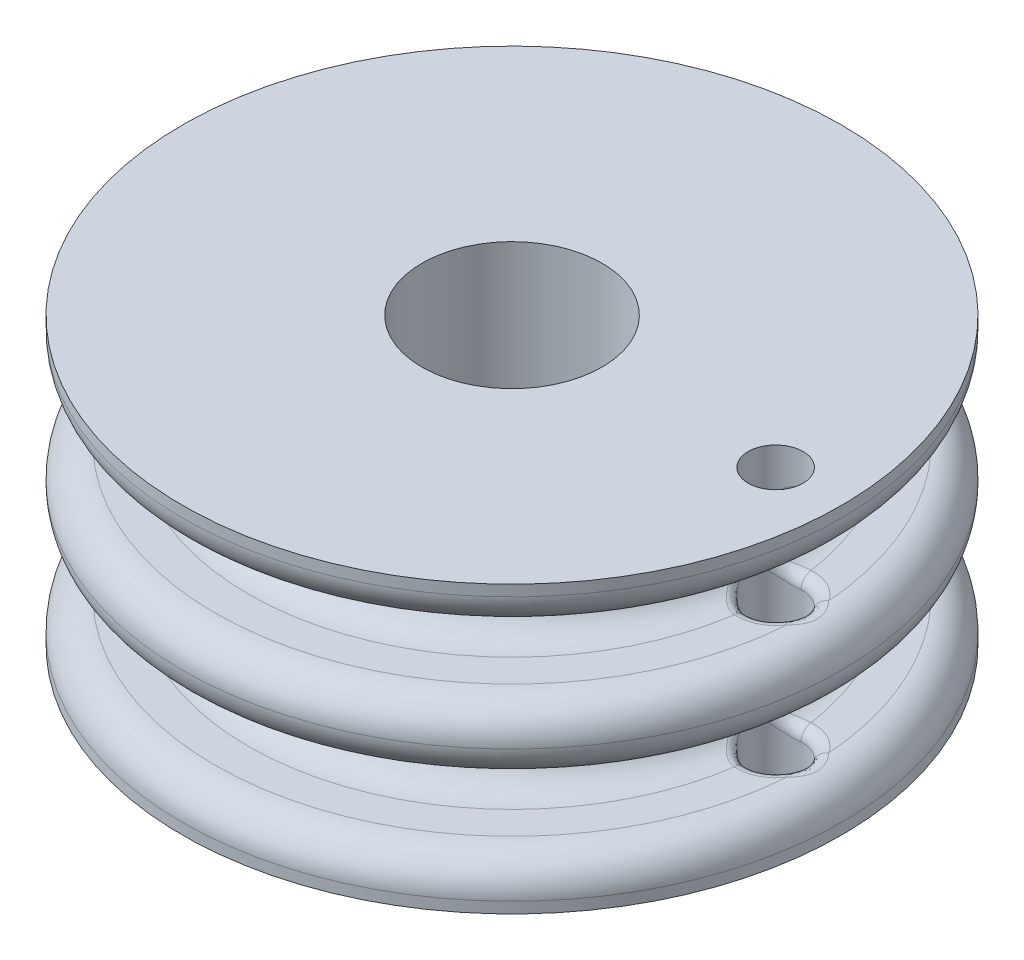
SolidWorks part; units mm, degrees
ref_plane "Plan de face" through (0, 0, 0) normal (0, 0, 1) x (1, 0, 0)
ref_plane "Plan de dessus" through (0, 0, 0) normal (0, 1, 0) x (1, 0, 0)
ref_plane "Plan de droite" through (0, 0, 0) normal (1, 0, 0) x (0, 0, -1)
sketch "Esquisse1" plane through (0, 0, 0) normal (0, 0, 1) x (1, 0, 0)
  line L0 (0, 0) -> (0, 13)
  line L1 (0, 13) -> (15, 13)
  line L2 (15, 13) -> (15, 11)
  line L3 (15, 11) -> (12, 11)
  line L4 (12, 8) -> (15, 8)
  line L5 (15, 8) -> (15, 5)
  line L6 (15, 5) -> (12, 5)
  line L7 (12, 2) -> (15, 2)
  line L8 (15, 2) -> (15, 0)
  line L9 (15, 0) -> (0, 0)
  line L10 (0, 13) -> (0, 26) construction
  arc A0 (12, 11) -> (12, 8) centre (12, 9.5) ccw
  arc A1 (12, 5) -> (12, 2) centre (12, 3.5) ccw
  dimension "D1" = 3
  dimension "D5" = 24
  dimension "D2" = 3
  dimension "D3" = 2
  dimension "D4" = 3
  dimension "D6" = 30
revolve "Révolution1" add sketch "Esquisse1" angle 360 about L10
fillet "Congé1" radius 1.5 4 edges at (0, 2, -15) (0, 5, -15) (0, 8, -15) (0, 11, -15)
sketch "Esquisse2" plane through (0, 13, 0) normal (0, 1, 0) x (1, 0, 0)
  circle A0 centre (12, 0) radius 1.25
  circle A2 centre (0, 0) radius 4.1
  circle A3 centre (0, 0) radius 12 construction
  dimension "D1" = 2.5
  dimension "D3" = 8.2
extrude "Enlèv. mat.-Extru.1" cut sketch "Esquisse2" against normal through all
fillet "Congé3" radius 0.5 8 edges at (13.25, 5, 0) (13.25, 2, 0) (13.25, 11, 0) (13.25, 8, 0) (10.7501, 4.3294, -0.0187) (10.7501, 2.6706, 0.0187) (10.7501, 10.3294, -0.0187) (10.7501, 8.6706, 0.0187)
